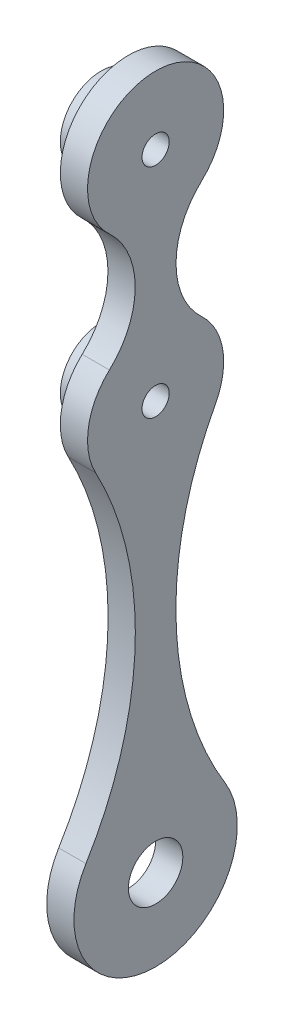
SolidWorks part; units mm, degrees
note: '?' marks a value the reader was unsure of.
ref_plane "Front Plane" through (0, 0, 0) normal (0, 0, 1) x (1, 0, 0)
ref_plane "Top Plane" through (0, 0, 0) normal (0, 1, 0) x (1, 0, 0)
ref_plane "Right Plane" through (0, 0, 0) normal (1, 0, 0) x (0, 0, -1)
sketch "Sketch1" plane through (0, 0, 0) normal (1, 0, 0) x (0, 0, -1)
  line L0 (0, 0) -> (0, -80) construction
  line L1 (0, -80) -> (0, -230) construction
  circle A0 centre (0, 0) radius 25
  circle A1 centre (0, -80) radius 25
  circle A2 centre (0, 0) radius 15
  circle A3 centre (0, -80) radius 15
  arc A4 (-16.9672, -18.3607) -> (-16.9672, -61.6393) centre (-36.9643, -40) cw
  arc A5 (16.9672, -18.3607) -> (16.9672, -61.6393) centre (36.9643, -40) ccw
  circle A6 centre (0, -230) radius 30
  circle A7 centre (0, -230) radius 10
  arc A8 (-22.0405, -91.7991) -> (-25.5857, -214.3357) centre (-130.7115, -149.9746) cw
  arc A9 (22.0405, -91.7991) -> (25.5857, -214.3357) centre (130.7115, -149.9746) ccw
  point P16 (-7.5, -40)
  point P18 (7.5, -40)
  point P25 (-7.5, -153.5393)
  point P26 (7.5, -153.5393)
  dimension "D1" = 50
  dimension "D2" = 50
  dimension "D5" = 10
  dimension "D6" = 15
  dimension "D7" = 60
  dimension "D3" = 80
  dimension "D8" = 15
  dimension "D9" = 150
  dimension "D4" = 10
extrude "Boss-Extrude1" add sketch "Sketch1" along normal blind 10
sketch "Sketch3" plane through (0, 0, 0) normal (-1, 0, 0) x (0, 0, 1)
  circle A0 centre (0, 0) radius 15
  circle A1 centre (0, -80) radius 15
  arc A2 (16.9672, -18.3607) -> (-16.9672, -18.3607) centre (0, 0) ccw construction
  arc A3 (22.0405, -91.7991) -> (16.9672, -61.6393) centre (0, -80) ccw construction
  dimension "D1" = 10
  dimension "D2" = 10
extrude "Boss-Extrude3" add sketch "Sketch3" along normal blind 10
sketch "Sketch4" plane through (-10, 0, 0) normal (-1, 0, 0) x (0, 0, 1)
  circle A2 centre (0, -80) radius 5
  circle A3 centre (0, -80) radius 5
  circle A5 centre (0, 0) radius 5
  circle A6 centre (0, 0) radius 5
  dimension "D1" = 10
  dimension "D2" = 10
extrude "Cut-Extrude1" cut sketch "Sketch4" against normal blind 20
ref_plane "Plane1" through (-5, 0, 0) normal (-1, 0, 0) x (0, 0, 1)
ref_axis "Axis1" through (10, 0, 0) along (-1, 0, 0)?
ref_axis "Axis2" through (10, -80, 0) along (-1, 0, 0)?
ref_plane "Plane2" through (5, 0, 0) normal (1, 0, 0) x (0, 0, -1)
ref_axis "Axis3" through (10, -230, 0) along (-1, 0, 0)?
ref_point "Point2"
ref_point "Point3"
ref_point "Point4"
